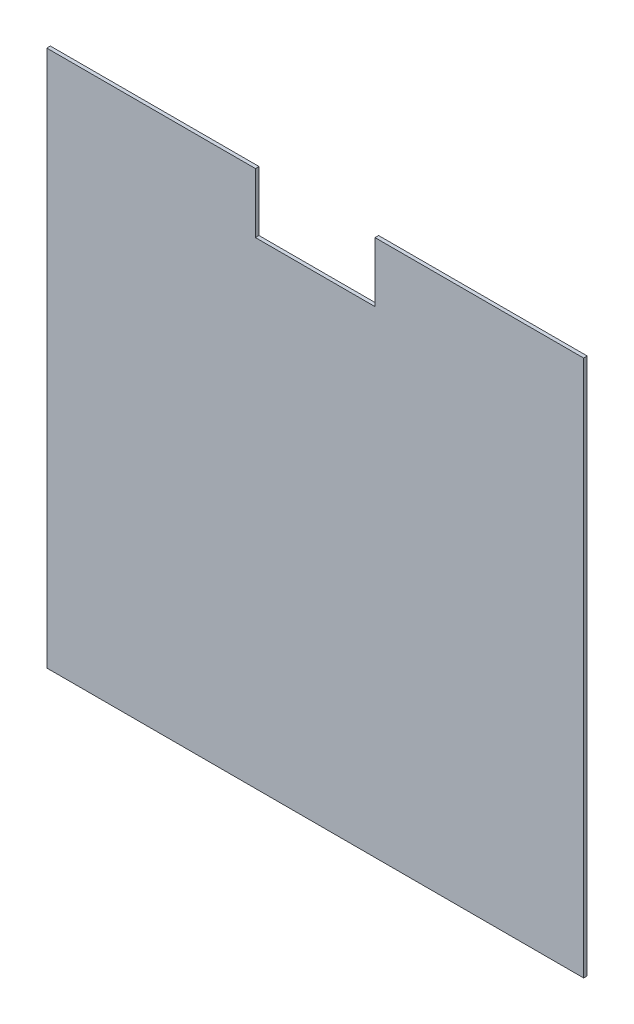
SolidWorks part; units mm, degrees
ref_plane "Piano frontale" through (0, 0, 0) normal (0, 0, 1) x (1, 0, 0)
ref_plane "Piano superiore" through (0, 0, 0) normal (0, 1, 0) x (1, 0, 0)
ref_plane "Piano destro" through (0, 0, 0) normal (1, 0, 0) x (0, 0, -1)
sketch "Schizzo1" plane through (0, 0, 0) normal (0, 0, 1) x (1, 0, 0)
  line L0 (0, 0) -> (0, 449)
  line L1 (0, 449) -> (174.5, 449)
  line L2 (449, 449) -> (449, 0)
  line L3 (449, 0) -> (0, 0)
  line L4 (174.5, 449) -> (174.5, 399)
  line L5 (174.5, 399) -> (274.5, 399)
  line L6 (274.5, 399) -> (274.5, 449)
  line L7 (274.5, 449) -> (449, 449)
  dimension "D1" = 449
  dimension "D2" = 449
  dimension "D3" = 100
  dimension "D4" = 50
extrude "Estrusione-Estrusione1" add sketch "Schizzo1" along normal blind 3
